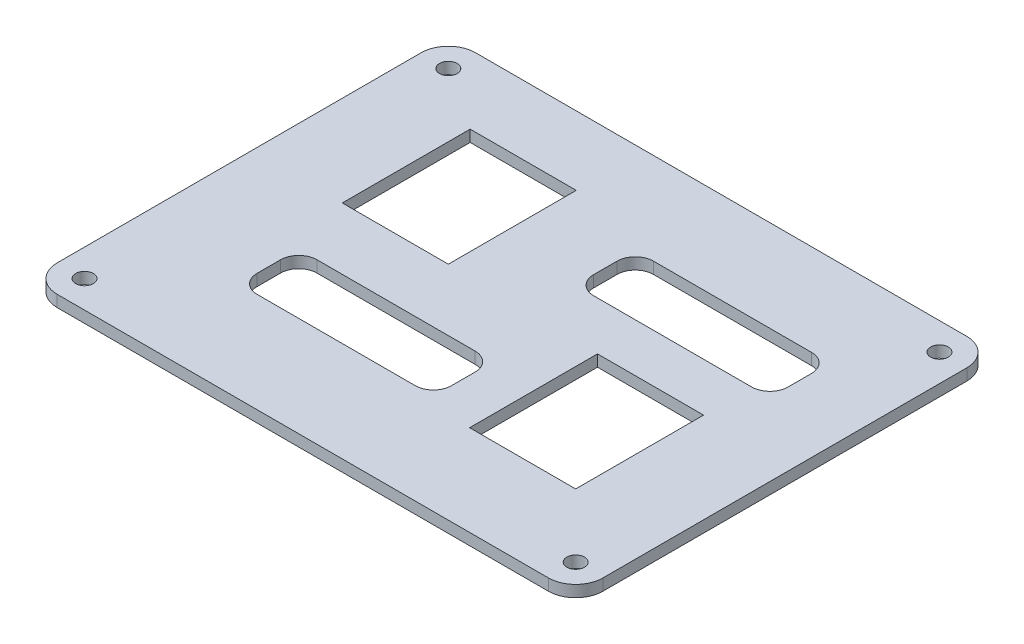
SolidWorks part; units mm, degrees
ref_plane "Front Plane" through (0, 0, 0) normal (0, 0, 1) x (1, 0, 0)
ref_plane "Top Plane" through (0, 0, 0) normal (0, 1, 0) x (1, 0, 0)
ref_plane "Right Plane" through (0, 0, 0) normal (1, 0, 0) x (0, 0, -1)
sketch "Sketch1" plane through (0, 0, 0) normal (0, 1, 0) x (1, 0, 0)
  line L1 (-37.8147, 171.0471) -> (232.1853, 171.0471)
  line L2 (-52.8147, 156.0471) -> (-52.8147, -43.9529)
  line L3 (-37.8147, -58.9529) -> (232.1853, -58.9529)
  line L4 (247.1853, 156.0471) -> (247.1853, -43.9529)
  arc A0 (-52.8147, -43.9529) -> (-37.8147, -58.9529) centre (-37.8147, -43.9529) ccw
  arc A1 (232.1853, -58.9529) -> (247.1853, -43.9529) centre (232.1853, -43.9529) ccw
  arc A2 (232.1853, 171.0471) -> (247.1853, 156.0471) centre (232.1853, 156.0471) cw
  arc A3 (-37.8147, 171.0471) -> (-52.8147, 156.0471) centre (-37.8147, 156.0471) ccw
  circle A4 centre (-37.8147, 156.0471) radius 4.85
  circle A5 centre (232.1853, 156.0471) radius 4.85
  circle A6 centre (232.1853, -43.9529) radius 4.85
  circle A7 centre (-37.8147, -43.9529) radius 4.85
  dimension "D1" = 15
  dimension "D4" = 9.7
  dimension "D2" = 230
  dimension "D3" = 300
extrude "Boss-Extrude1" add sketch "Sketch1" along normal blind 6.35
sketch "Sketch2" plane through (0, 0, 0) normal (0, -1, 0) x (1, 0, 0)
  line L12 (197.3353, -61.1971) -> (139.0353, -61.1971)
  line L13 (197.3353, -61.1971) -> (197.3353, 9.1029)
  line L14 (247.1853, -56.0471) -> (-52.8147, -56.0471) construction
  line L15 (247.1853, 43.9529) -> (247.1853, -156.0471) construction
  line L16 (-52.8147, -156.0471) -> (-52.8147, 43.9529) construction
  line L21 (97.1853, -56.0471) -> (97.1853, -171.0471) construction
  line L22 (232.1853, -171.0471) -> (-37.8147, -171.0471) construction
  line L23 (-2.9647, -62.8971) -> (55.3353, -62.8971)
  line L24 (-2.9647, -62.8971) -> (-2.9647, -133.1971)
  line L25 (-2.9647, -133.1971) -> (55.3353, -133.1971)
  line L26 (55.3353, -62.8971) -> (55.3353, -133.1971)
  line L31 (197.3353, 9.1029) -> (139.0353, 9.1029)
  line L33 (139.0353, -61.1971) -> (139.0353, 9.1029)
  line L34 (18.9625, -132.6971) -> (33.4082, -132.6971) construction
  line L35 (-2.4647, -105.6971) -> (-2.4647, -78.3971) construction
  line L36 (54.8353, -78.3971) -> (54.8353, -105.6971) construction
  line L37 (8.5353, -63.3971) -> (43.8353, -63.3971) construction
  line L38 (150.5353, 8.6029) -> (185.8353, 8.6029) construction
  line L39 (196.8353, -6.3971) -> (196.8353, -33.6971) construction
  line L40 (139.5353, -33.6971) -> (139.5353, -6.3971) construction
  line L41 (160.9625, -60.6971) -> (175.4082, -60.6971) construction
  dimension "D1" = 0.5
  dimension "D2" = 0.5
  dimension "D3" = 0.5
  dimension "D4" = 0.5
  dimension "D5" = 0.5
  dimension "D6" = 0.5
  dimension "D7" = 0.5
  dimension "D8" = 0.5
extrude "Cut-Extrude1" cut sketch "Sketch2" against normal up to surface (6.35 mm away) up to face at (232.1853, 6.35, 48.8029)
sketch "Sketch3" plane through (0, 0, 0) normal (0, -1, 0) x (1, 0, 0)
  line L0 (17.1075, -28.9007) -> (104.0414, -28.9007)
  line L1 (110.2512, -120.7454) -> (197.1851, -120.7454)
  line L2 (100.2512, -110.7454) -> (100.2512, -97.8165)
  line L3 (110.2512, -87.8165) -> (197.1851, -87.8165)
  line L4 (207.1851, -110.7454) -> (207.1851, -97.8165)
  line L5 (7.1075, -18.9007) -> (7.1075, -5.9718)
  line L6 (17.1075, 4.0282) -> (104.0414, 4.0282)
  line L7 (114.0414, -18.9007) -> (114.0414, -5.9718)
  arc A0 (100.2512, -97.8165) -> (110.2512, -87.8165) centre (110.2512, -97.8165) cw
  arc A1 (197.1851, -87.8165) -> (207.1851, -97.8165) centre (197.1851, -97.8165) cw
  arc A2 (197.1851, -120.7454) -> (207.1851, -110.7454) centre (197.1851, -110.7454) ccw
  arc A3 (110.2512, -120.7454) -> (100.2512, -110.7454) centre (110.2512, -110.7454) cw
  arc A4 (7.1075, -5.9718) -> (17.1075, 4.0282) centre (17.1075, -5.9718) cw
  arc A5 (104.0414, 4.0282) -> (114.0414, -5.9718) centre (104.0414, -5.9718) cw
  arc A6 (104.0414, -28.9007) -> (114.0414, -18.9007) centre (104.0414, -18.9007) ccw
  arc A7 (17.1075, -28.9007) -> (7.1075, -18.9007) centre (17.1075, -18.9007) cw
  dimension "D1" = 10
  dimension "D2" = 10
extrude "Cut-Extrude2" cut sketch "Sketch3" against normal up to surface (6.35 mm away) up to face at (168.1853, 6.35, -26.0471)
